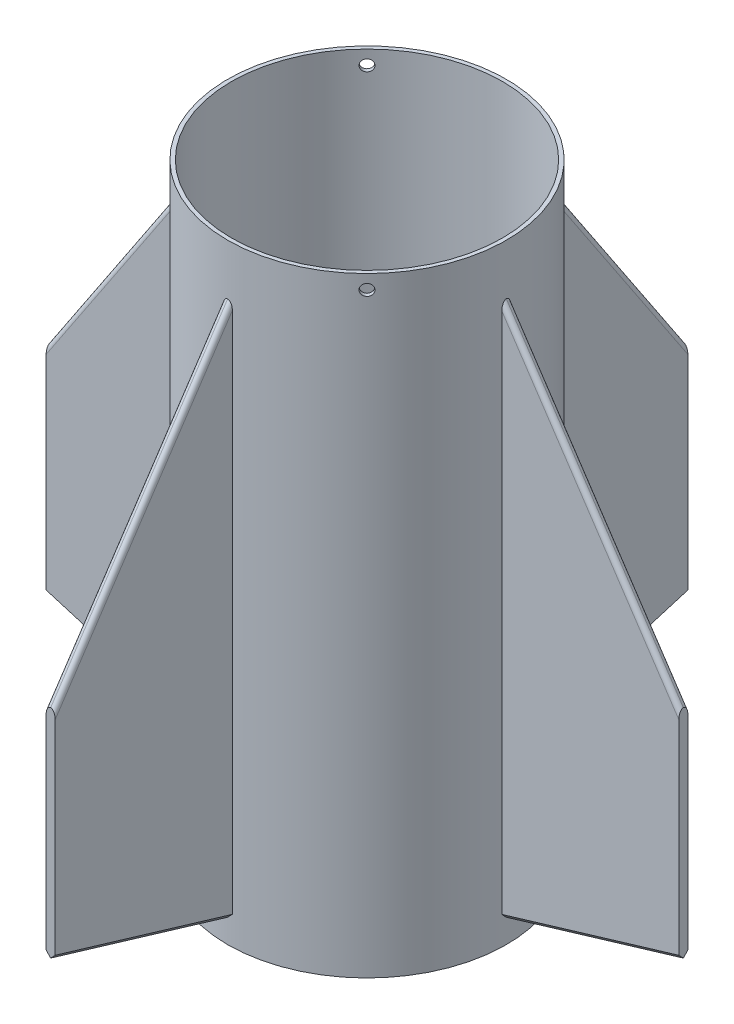
SolidWorks part; units mm, degrees
ref_plane "Front Plane" through (0, 0, 0) normal (0, 0, 1) x (1, 0, 0)
ref_plane "Top Plane" through (0, 0, 0) normal (0, 1, 0) x (1, 0, 0)
ref_plane "Right Plane" through (0, 0, 0) normal (1, 0, 0) x (0, 0, -1)
sketch "Sketch1" plane through (0, 0, 0) normal (0, 1, 0) x (1, 0, 0)
  circle A0 centre (0, 0) radius 76.2
  circle A1 centre (0, 0) radius 78.359
  dimension "D1" = 152.4
  dimension "D2" = 156.718
extrude "Boss-Extrude1" add sketch "Sketch1" along normal blind 342.9
sketch "Sketch2" plane through (0, 0, 0) normal (0, 0, 1) x (1, 0, 0)
  line L0 (76.2, 317.5) -> (76.2, 12.7)
  line L1 (76.2, 12.7) -> (177.8, 43.18)
  line L2 (177.8, 43.18) -> (177.8, 165.1)
  line L3 (177.8, 165.1) -> (76.2, 317.5)
  dimension "D1" = 76.2
  dimension "D2" = 121.92
  dimension "D3" = 101.6
  dimension "D4" = 304.8
  dimension "D5" = 152.4
  dimension "D6" = 12.7
extrude "Boss-Extrude2" add sketch "Sketch2" along normal blind 2.54 and the other way blind 2.54 separate body
sketch "Sketch3" plane through (0, 0, 0) normal (0, 0, 1) x (1, 0, 0)
  line L0 (0, -69.284) -> (0, 493.4849) construction
fillet "Fillet2" radius 2.54 2 edges at (127, 241.3, -2.54) (127, 241.3, 2.54)
chamfer "Chamfer2" distance 2.54 angle 45 2 edges at (127, 27.94, -2.54) (127, 27.94, 2.54)
pattern_circular "CirPattern1" count 4 over 360 about axis through (0, -69.284, 0) along (0, 1, 0) of bodies 102
ref_plane "Plane1" through (0, 0, 0) normal (-0.7071, 0, -0.7071) x (-0.7071, 0, 0.7071)
sketch "Sketch4" plane through (0, 0, 0) normal (-0.7071, 0, -0.7071) x (-0.7071, 0, 0.7071)
  line L0 (0, 342.9) -> (0, 0) construction
  circle A0 centre (0, 334.9498) radius 3.175
  point P2 (0, 334.9498)
  dimension "D1" = 6.35
  dimension "D2" = 334.9498
extrude "Cut-Extrude1" cut sketch "Sketch4" against normal through all contours A0
pattern_circular "CirPattern2" count 4 over 360 about axis through (0, -69.284, 0) along (0, 1, 0) of "Cut-Extrude1" reverse direction yes
